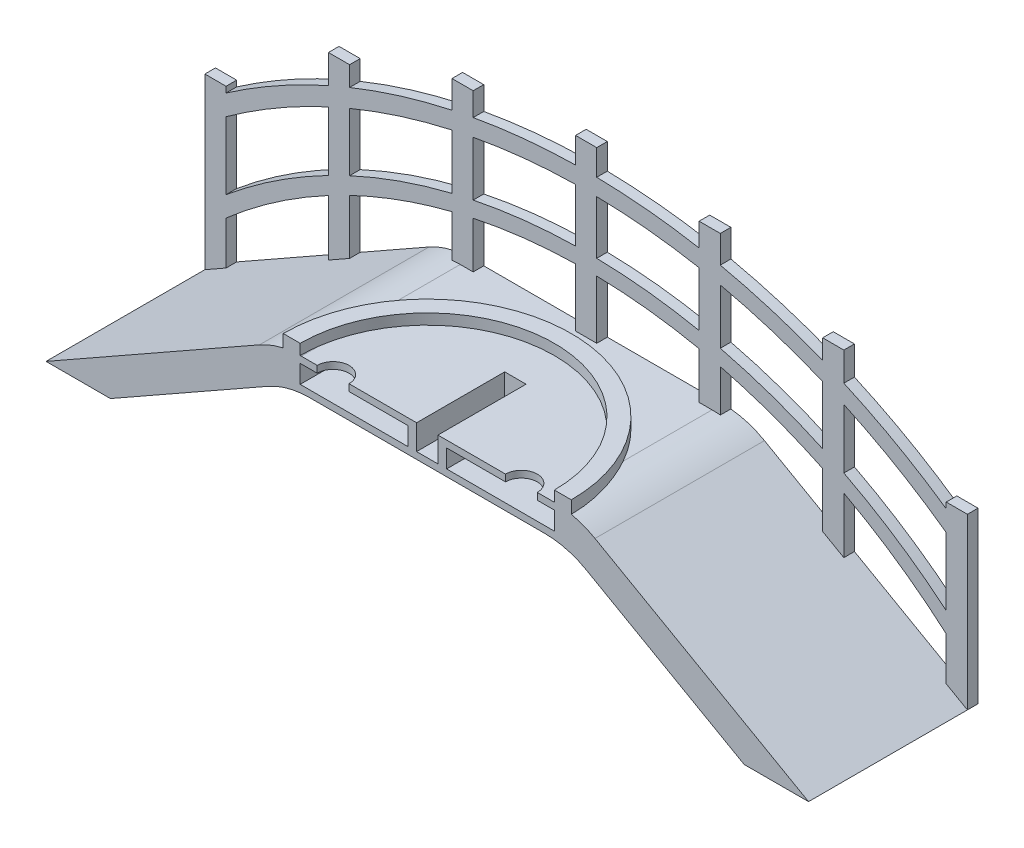
SolidWorks part; units mm, degrees
ref_plane "Front Plane" through (0, 0, 0) normal (0, 0, 1) x (1, 0, 0)
ref_plane "Top Plane" through (0, 0, 0) normal (0, 1, 0) x (1, 0, 0)
ref_plane "Right Plane" through (0, 0, 0) normal (1, 0, 0) x (0, 0, -1)
sketch "Sketch5" plane through (0, 0, 0) normal (0, 0, 1) x (1, 0, 0)
  line L0 (1.175, -2.0712) -> (16.6334, 6.6983)
  line L1 (19.1382, 9.9064) -> (38.0118, 9.9064)
  line L2 (0, 0) -> (16.005, 9.0795)
  line L3 (41.145, 9.0795) -> (57.15, 0)
  line L4 (0, 0) -> (17.4625, 0) construction
  line L5 (57.15, 0) -> (39.6875, 0) construction
  line L6 (19.7666, 7.5251) -> (37.3834, 7.5251)
  line L7 (40.5166, 6.6983) -> (55.975, -2.0712)
  line L8 (0, 0) -> (4.826, 0)
  line L9 (57.15, 0) -> (52.324, 0)
  line L10 (0, 0) -> (0, 9.525)
  line L11 (57.15, 0) -> (57.15, 9.525)
  line L12 (28.575, 9.9064) -> (28.575, 19.4314) construction
  line L13 (28.575, 9.9064) -> (28.575, 6.7314) construction
  line L14 (0, 0) -> (1.5875, 0)
  line L15 (0, 0) -> (0, 12.7)
  line L16 (0, 12.7) -> (1.5875, 12.7)
  line L17 (1.5875, 0) -> (1.5875, 12.7)
  line L18 (29.3687, 6.7314) -> (27.7812, 6.7314)
  line L19 (29.3687, 6.7314) -> (29.3687, 22.6064)
  line L20 (29.3687, 22.6064) -> (27.7812, 22.6064)
  line L21 (27.7812, 6.7314) -> (27.7812, 22.6064)
  line L22 (1.5875, 9.2118) -> (9.2604, 9.2118) construction
  line L23 (9.2604, 18.7284) -> (10.8479, 18.7284)
  line L24 (9.2604, 18.7284) -> (9.2604, 2.8534)
  line L25 (9.2604, 2.8534) -> (10.8479, 2.8534)
  line L26 (10.8479, 18.7284) -> (10.8479, 2.8534)
  line L27 (18.5208, 21.6681) -> (20.1083, 21.6681)
  line L28 (18.5208, 21.6681) -> (18.5208, 5.7931)
  line L29 (18.5208, 5.7931) -> (20.1083, 5.7931)
  line L30 (20.1083, 21.6681) -> (20.1083, 5.7931)
  line L31 (10.8479, 8.208) -> (18.5208, 8.208) construction
  line L32 (20.1083, 13.1596) -> (27.7812, 13.1596) construction
  line L33 (10.0542, 18.7284) -> (10.0542, 15.5534) construction
  line L34 (19.3146, 21.6681) -> (19.3146, 18.4931) construction
  line L35 (57.15, 0) -> (52.324, 0)
  line L36 (38.6292, 21.6681) -> (37.0417, 21.6681)
  line L37 (38.6292, 21.6681) -> (38.6292, 5.7931)
  line L38 (37.0417, 21.6681) -> (37.0417, 5.7931)
  line L39 (38.6292, 5.7931) -> (37.0417, 5.7931)
  line L40 (47.8896, 2.8534) -> (46.3021, 2.8534)
  line L41 (47.8896, 18.7284) -> (46.3021, 18.7284)
  line L42 (46.3021, 18.7284) -> (46.3021, 2.8534)
  line L43 (47.8896, 18.7284) -> (47.8896, 2.8534)
  line L44 (57.15, 12.7) -> (55.5625, 12.7)
  line L45 (57.15, 0) -> (57.15, 12.7)
  line L46 (57.15, 0) -> (57.15, 9.525)
  line L47 (55.5625, 0) -> (55.5625, 12.7)
  line L48 (18.0909, 7.5251) -> (39.0591, 7.5251) construction
  line L49 (39.0591, 7.5251) -> (55.975, -2.0712) construction
  line L50 (17.4625, 9.9064) -> (39.6875, 9.9064) construction
  line L51 (39.6875, 9.9064) -> (57.15, 0) construction
  line L52 (1.175, -2.0712) -> (18.0909, 7.5251) construction
  line L53 (0, 0) -> (17.4625, 9.9064) construction
  arc A0 (0, 9.525) -> (57.15, 9.525) centre (28.575, -26.7342) cw
  arc A1 (0, 11.1125) -> (57.15, 11.1125) centre (28.575, -26.7342) cw
  arc A2 (37.3834, 7.5251) -> (40.5166, 6.6983) centre (37.3834, 1.1751) cw
  arc A3 (38.0118, 9.9064) -> (41.145, 9.0795) centre (38.0118, 3.5564) cw
  arc A4 (16.6334, 6.6983) -> (19.7666, 7.5251) centre (19.7666, 1.1751) cw
  arc A5 (19.1382, 9.9064) -> (16.005, 9.0795) centre (19.1382, 3.5564) ccw
  point P47 (57.15, 10.9464)
  point P65 (39.6875, 9.9064)
  dimension "D12" = 6.35
  dimension "D1" = 57.15
  dimension "D3" = 2.3813
  dimension "D4" = 9.525
  dimension "D5" = 1.5875
  dimension "D6" = 12.7
  dimension "D7" = 1.5875
  dimension "D8" = 15.875
  dimension "D9" = 12.7
  dimension "D10" = 3.175
  dimension "D11" = 1.5875
extrude "Boss-Extrude1" add sketch "Sketch5" along normal blind 12.7 contours L25 L24 L2 L17 L8 L0 | L8 L17 L2 | L26 L2 L24 L25 L0 | L28 A5 L2 L26 L0 A4 | L1 A5 L28 A4 L6 L30 | L1 L30 L6 L21 | L21 L6 L19 L1 | L38 L1 L19 L6 | A3 L1 L38 L6 A2 L37 | A3 L37 A2 L7 L42 L3 | L43 L3 L42 L7 L40 | L35 L47 L3 L43 L40 L7 | L47 L9 L3 region at (5.8986, 2.0945, 0) region at (10.0683, 4.3725, 0) region at (1.0583, 0.3002, 0) region at (14.6384, 6.8871, 0) region at (19.3092, 8.6975, 0) region at (23.9448, 8.7158, 0) region at (28.575, 8.7158, 0) region at (33.2052, 8.7158, 0) region at (37.8408, 8.6975, 0) region at (42.5116, 6.8871, 0) region at (47.0817, 4.3725, 0) region at (51.2514, 2.0945, 0) region at (56.0917, 0.3002, 0)
extrude "Boss-Extrude2" add sketch "Sketch5<4>" along normal blind 0.7937 separate body contours A1 L15 A0 L17 | A1 L17 A0 L24 | A1 L24 A0 L26 | A1 L26 A0 L28 | A1 L28 A0 L30 | A1 L30 A0 L21 | A1 L21 A0 L19 | A1 L19 A0 L38 | A1 L38 A0 L37 | A1 L37 A0 L42 | A1 L42 A0 L43 | A1 L43 A0 L47 | A1 L47 A0 L45 region at (0.7896, 10.9105, 0) region at (5.3546, 13.8101, 0) region at (10.0521, 16.234, 0) region at (14.65, 17.8791, 0) region at (19.3137, 19.1317, 0) region at (23.9343, 19.7758, 0) region at (28.575, 20.0576, 0) region at (33.2157, 19.7758, 0) region at (37.8363, 19.1317, 0) region at (42.5, 17.8791, 0) region at (47.0979, 16.234, 0) region at (51.7954, 13.8101, 0) region at (56.3604, 10.9105, 0)
sketch "Sketch5<4>" plane through (0, 0, 0) normal (0, 0, 1) x (1, 0, 0) same geometry as "Sketch5"
extrude "Boss-Extrude6" add sketch "Sketch5<7>" along normal blind 0.7937 contours A0 L10 L2 L17 | A1 L15 A0 L17 | L15 A1 L17 L16 | A0 L24 L2 L26 | A1 L24 A0 L26 | L24 A1 L26 L23 | L26 L2 L24 L25 L0 | L26 L0 L25 | A4 L28 L29 L30 L6 | L1 A5 L28 A4 L6 L30 | A5 L1 L30 A0 L28 | A1 L28 A0 L30 | L28 A1 L30 L27 | L21 A1 L19 L20 | A1 L21 A0 L19 | A0 L21 L1 L19 | L21 L6 L19 L1 | L21 L18 L19 L6 | L47 L9 L3 | A0 L47 L3 L11 | A1 L47 A0 L45 | L47 A1 L45 L44 | A0 L42 L3 L43 | A1 L42 A0 L43 | L42 A1 L43 L41 | L43 L3 L42 L7 L40 | L7 L42 L40 | A2 L6 L38 L39 L37 | A3 L1 L38 L6 A2 L37 | L1 A3 L37 A0 L38 | L38 A1 L37 L36 | A1 L38 A0 L37 region at (10.0683, 4.3725, 0) region at (10.5172, 3.041, 0) region at (0.7978, 5.2939, 0) region at (10.0514, 10.6257, 0) region at (0.7896, 10.9105, 0) region at (19.3237, 6.6434, 0) region at (19.3092, 8.6975, 0) region at (10.0521, 16.234, 0) region at (0.6427, 12.1428, 0) region at (19.3193, 14.1971, 0) region at (10.0049, 17.8134, 0) region at (19.3137, 19.1317, 0) region at (19.2925, 20.7184, 0) region at (28.575, 8.7158, 0) region at (28.575, 7.1283, 0) region at (28.575, 14.6677, 0) region at (28.575, 20.0576, 0) region at (28.575, 21.6463, 0) region at (37.8408, 8.6975, 0) region at (37.8263, 6.6434, 0) region at (37.8307, 14.1971, 0) region at (37.8363, 19.1317, 0) region at (37.8575, 20.7184, 0) region at (47.0986, 10.6257, 0) region at (47.0979, 16.234, 0) region at (47.1451, 17.8134, 0) region at (47.0817, 4.3725, 0) region at (46.6328, 3.041, 0) region at (56.3522, 5.2939, 0) region at (56.3604, 10.9105, 0) region at (56.5073, 12.1428, 0) region at (56.0917, 0.3002, 0)
sketch "Sketch5<7>" plane through (0, 0, 0) normal (0, 0, 1) x (1, 0, 0) same geometry as "Sketch5"
sketch "Sketch6" plane through (0, 0, 0) normal (0, 0, -1) x (-1, 0, 0)
  line L0 (-57.15, 0) -> (-57.15, 12.7) construction
  line L1 (0, 0) -> (0, 12.7) construction
  line L2 (-57.15, 4.2704) -> (-57.15, 2.6829)
  line L3 (0, 2.6829) -> (0, 4.2704)
  arc A0 (-57.15, 4.2704) -> (0, 4.2704) centre (-28.575, -26.7342) cw
  arc A1 (-57.15, 2.6829) -> (0, 2.6829) centre (-28.575, -26.7342) cw
  arc A2 (-29.3687, 19.4246) -> (-37.0417, 18.6484) centre (-28.575, -26.7342) ccw construction
  dimension "D1" = 1.5875
extrude "Boss-Extrude7" add sketch "Sketch6" against normal blind 0.7937
sketch "Sketch7" plane through (0, 0, 12.7) normal (0, 0, 1) x (1, 0, 0)
  line L0 (28.575, 9.9064) -> (19.05, 9.9064)
  line L1 (19.1382, 9.9064) -> (38.0118, 9.9064) construction
  line L2 (19.05, 9.9064) -> (19.05, 9.3984)
  line L3 (19.7666, 7.5251) -> (37.3834, 7.5251) construction
  line L4 (19.05, 9.3984) -> (38.1, 9.3984)
  line L5 (19.05, 9.3984) -> (19.05, 8.0331)
  line L6 (19.05, 8.0331) -> (38.1, 8.0331)
  line L7 (38.1, 9.3984) -> (38.1, 8.0331)
  dimension "D1" = 9.525
  dimension "D2" = 0.508
  dimension "D3" = 0.508
  dimension "D4" = 19.05
extrude "Cut-Extrude1" cut sketch "Sketch7" against normal blind 9.525 contours L7 L4 L5 L6 region at (28.575, 8.7158, 12.7)
sketch "Sketch8" plane through (0, 9.9064, 0) normal (0, 1, 0) x (1, 0, 0)
  line L0 (19.1382, -12.7) -> (38.0118, -12.7) construction
  line L1 (21.5195, -12.7) -> (19.1382, -12.7)
  line L2 (35.6305, -12.7) -> (38.0118, -12.7)
  line L4 (29.3751, -19.304) -> (27.7749, -19.304)
  line L5 (29.3751, -19.304) -> (29.3751, -6.096)
  line L6 (29.3751, -6.096) -> (27.7749, -6.096)
  line L7 (27.7749, -19.304) -> (27.7749, -6.096)
  line L8 (29.3751, -19.304) -> (27.7749, -6.096) construction
  line L9 (29.3751, -6.096) -> (27.7749, -19.304) construction
  circle A0 centre (21.5195, -12.7) radius 1.1906
  circle A1 centre (35.6305, -12.7) radius 1.1906
  point P8 (28.575, -12.7)
  line M5 (19.1382, -12.7) -> (38.0118, -12.7)
  dimension "D1" = 2.3813
  dimension "D2" = 2.3813
  dimension "D3" = 2.3813
  dimension "D4" = 1.6002
  dimension "D5" = 13.208
extrude "Cut-Extrude2" cut sketch "Sketch8" against normal blind 1.397 contours A0 L1 M5 | A1 M5 | L7 L5 L6 M5 region at (21.5195, 9.9064, 12.1947) region at (35.6305, 9.9064, 12.1947) region at (28.575, 9.9064, 9.398)
sketch "Sketch10" plane through (0, 8.0331, 0) normal (0, 1, 0) x (1, 0, 0)
  line L0 (19.05, -12.7) -> (38.1, -12.7) construction
  line L1 (30.0256, -19.9033) -> (27.1244, -19.9033)
  line L2 (30.0256, -19.9033) -> (30.0256, -5.4967)
  line L3 (30.0256, -5.4967) -> (27.1244, -5.4967)
  line L4 (27.1244, -19.9033) -> (27.1244, -5.4967)
  line L5 (30.0256, -19.9033) -> (27.1244, -5.4967) construction
  line L6 (30.0256, -5.4967) -> (27.1244, -19.9033) construction
  line L7 (27.1244, -12.7) -> (30.0256, -12.7)
  line L8 (29.3751, -19.304) -> (27.7749, -19.304)
  line L9 (29.3751, -19.304) -> (29.3751, -6.096)
  line L10 (29.3751, -6.096) -> (27.7749, -6.096)
  line L11 (27.7749, -19.304) -> (27.7749, -6.096)
  line L12 (29.3751, -19.304) -> (27.7749, -6.096) construction
  line L13 (29.3751, -6.096) -> (27.7749, -19.304) construction
  point P0 (28.575, -12.7)
  point P7 (28.575, -12.7)
  line M1 (19.05, -12.7) -> (38.1, -12.7)
extrude "Boss-Extrude8" add sketch "Sketch10" along normal blind 1.397 contours L11 L10 L9 L7 L2 L3 L4 M1 region at (29.7004, 8.0331, 12.6223)
sketch "Sketch11" plane through (0, 9.9064, 0) normal (0, 1, 0) x (1, 0, 0)
  line L0 (27.7749, -12.7) -> (29.3751, -12.7) construction
  line L1 (17.78, -12.7) -> (39.37, -12.7)
  circle A0 centre (28.575, -12.7) radius 9.525
  circle A1 centre (28.575, -12.7) radius 10.795
  line M9 (38.0118, -12.7) -> (38.0118, -0.7937)
  line M19 (19.1382, -0.7937) -> (19.1382, -12.7)
  dimension "D1" = 19.05
  dimension "D2" = 21.59
extrude "Boss-Extrude9" add sketch "Sketch11" along normal blind 0.7937 and the other way blind 0.254 contours A1 A0 M9 M19 | A1 L1 A0 M19 | L1 A1 A0 M9 region at (18.5837, 9.9064, 10.6925) region at (19.3495, 9.9064, 9.4323) region at (38.5663, 9.9064, 10.6925)
